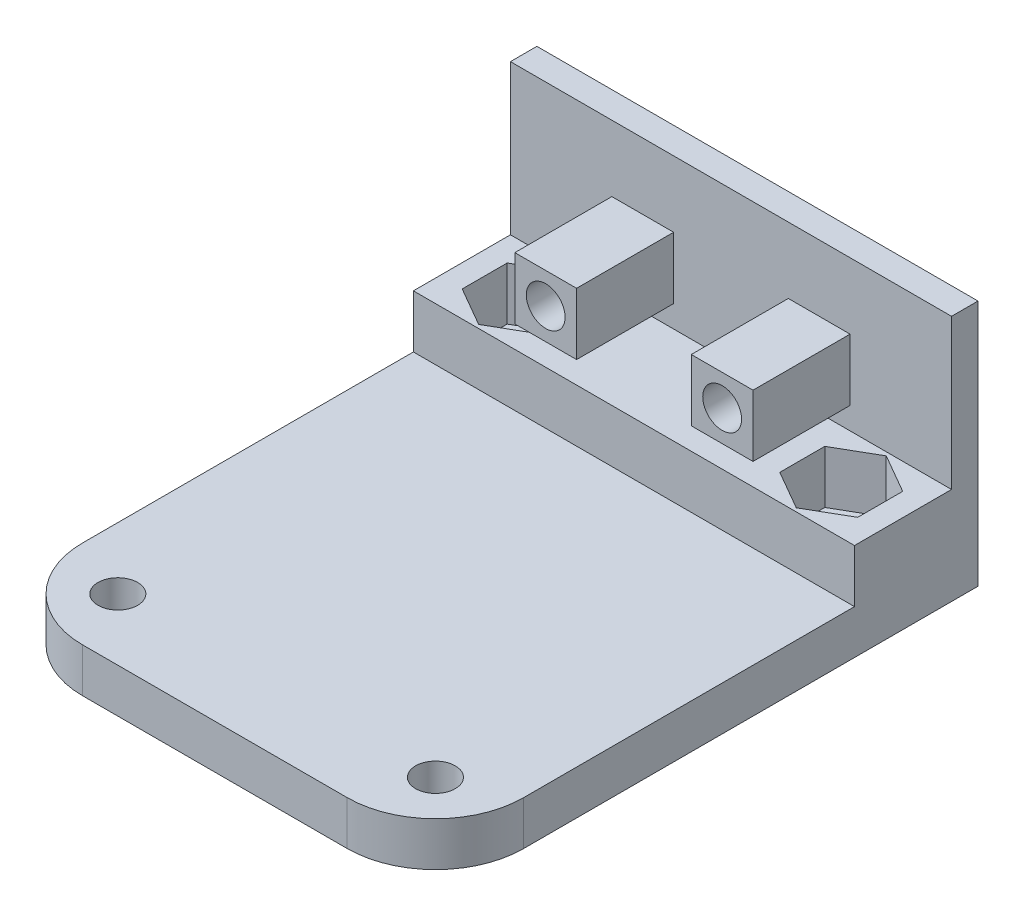
SolidWorks part; units mm, degrees
ref_plane "Front Plane" through (0, 0, 0) normal (0, 0, 1) x (1, 0, 0)
ref_plane "Top Plane" through (0, 0, 0) normal (0, 1, 0) x (1, 0, 0)
ref_plane "Right Plane" through (0, 0, 0) normal (1, 0, 0) x (0, 0, -1)
sketch "Sketch1" plane through (0, 0, 0) normal (0, 0, 1) x (1, 0, 0)
  line L1 (-25, 16.5) -> (25, 16.5)
  line L2 (-25, 16.5) -> (-25, -16.5)
  line L3 (-25, -16.5) -> (25, -16.5)
  line L4 (25, 16.5) -> (25, -16.5)
  line L5 (-25, 16.5) -> (25, -16.5) construction
  line L6 (-25, -16.5) -> (25, 16.5) construction
  point P0 (0, 0)
  dimension "D1" = 33
  dimension "D2" = 50
extrude "Boss-Extrude1" add sketch "Sketch1" along normal blind 3 contours L2 L3 L4 L1
sketch "Sketch2" plane through (0, 0, 3) normal (0, 0, 1) x (1, 0, 0)
  line L0 (25, 16.5) -> (25, -16.5) construction
  line L1 (-25, -16.5) -> (25, -16.5)
  line L2 (-25, -16.5) -> (-25, -11.5)
  line L3 (-25, -11.5) -> (25, -11.5)
  line L4 (25, -16.5) -> (25, -11.5)
  dimension "D1" = 5
extrude "Boss-Extrude2" add sketch "Sketch2" along normal blind 58.5
sketch "Sketch3" plane through (0, -11.5, 0) normal (0, 1, 0) x (1, 0, 0)
  line L0 (-25, -51.5) -> (-25, -61.5)
  line L1 (-25, -61.5) -> (-15, -61.5)
  line L2 (15, -61.5) -> (25, -61.5)
  line L3 (25, -61.5) -> (25, -51.5)
  arc A1 (15, -61.5) -> (25, -51.5) centre (15, -51.5) ccw construction
  arc A2 (15, -61.5) -> (25, -51.5) centre (15, -51.5) ccw
  arc A3 (-25, -51.5) -> (-15, -61.5) centre (-15, -51.5) ccw construction
  arc A4 (-25, -51.5) -> (-15, -61.5) centre (-15, -51.5) ccw
  circle A5 centre (-18, -54.5) radius 2.2479 construction
  circle A6 centre (-18, -54.5) radius 2.2479
  circle A7 centre (18, -54.5) radius 2.2479 construction
  circle A8 centre (18, -54.5) radius 2.2479
  circle A9 centre (-18, -8.5) radius 2.2479 construction
  circle A10 centre (-18, -8.5) radius 2.2479
  circle A11 centre (18, -8.5) radius 2.2479 construction
  circle A12 centre (18, -8.5) radius 2.2479
extrude "Cut-Extrude1" cut sketch "Sketch3" against normal up to surface (5 mm away) up to face at (0, -16.5, 30.75)
sketch "Sketch4" plane through (0, 0, 3) normal (0, 0, 1) x (1, 0, 0)
  line L5 (-13.5006, 4) -> (-6.5006, 4)
  line L6 (-13.5006, 4) -> (-13.5006, -3)
  line L7 (-13.5006, -3) -> (-6.5006, -3)
  line L8 (-6.5006, 4) -> (-6.5006, -3)
  line L9 (-13.5006, 4) -> (-6.5006, -3) construction
  line L10 (-13.5006, -3) -> (-6.5006, 4) construction
  line L11 (6.4994, 4) -> (13.4994, 4)
  line L12 (6.4994, 4) -> (6.4994, -3)
  line L13 (6.4994, -3) -> (13.4994, -3)
  line L14 (13.4994, 4) -> (13.4994, -3)
  line L15 (6.4994, 4) -> (13.4994, -3) construction
  line L16 (6.4994, -3) -> (13.4994, 4) construction
  circle A0 centre (-10.0006, 0.5) radius 2.2 construction
  circle A1 centre (-10.0006, 0.5) radius 2.2
  circle A2 centre (9.9994, 0.5) radius 2.2 construction
  circle A3 centre (9.9994, 0.5) radius 2.2
  dimension "D1" = 7
extrude "Boss-Extrude3" add sketch "Sketch4" along normal blind 11
sketch "Sketch5" plane through (0, 0, 14) normal (0, 0, 1) x (1, 0, 0)
  circle A0 centre (9.9994, 0.5) radius 2.2 construction
  circle A1 centre (9.9994, 0.5) radius 2.2
  circle A2 centre (-10.0006, 0.5) radius 2.2 construction
  circle A3 centre (-10.0006, 0.5) radius 2.2
extrude "Cut-Extrude2" cut sketch "Sketch5" against normal up to surface (14 mm away) up to face at (0, 0, 0)
sketch "Sketch6" plane through (0, 0, 3) normal (0, 0, 1) x (1, 0, 0)
  line L0 (25, 16.5) -> (25, -11.5) construction
  line L1 (-25, 16.5) -> (25, 16.5)
  line L2 (-25, 16.5) -> (-25, 11.5)
  line L3 (-25, 11.5) -> (25, 11.5)
  line L4 (25, 16.5) -> (25, 11.5)
  dimension "D1" = 5
extrude "Cut-Extrude3" cut sketch "Sketch6" against normal up to surface (3 mm away) up to face at (7.7994, 0.5, 0)
sketch "Sketch7" plane through (0, -11.5, 0) normal (0, 1, 0) x (1, 0, 0)
  line L0 (25, -51.5) -> (25, -3) construction
  line L1 (-25, -3) -> (25, -3)
  line L2 (-25, -3) -> (-25, -14)
  line L3 (-25, -14) -> (25, -14)
  line L4 (25, -3) -> (25, -14)
  dimension "D1" = 11
extrude "Boss-Extrude4" add sketch "Sketch7" along normal blind 6
sketch "Sketch8" plane through (0, -5.5, 0) normal (0, 1, 0) x (1, 0, 0)
  line L1 (-18, -3.4) -> (-22.4167, -5.95)
  line L2 (-22.4167, -5.95) -> (-22.4167, -11.05)
  line L3 (-22.4167, -11.05) -> (-18, -13.6)
  line L4 (-18, -13.6) -> (-13.5833, -11.05)
  line L5 (-13.5833, -11.05) -> (-13.5833, -5.95)
  line L6 (-13.5833, -5.95) -> (-18, -3.4)
  line L8 (0, -18.15) -> (0, 18.15) construction
  line L9 (13.5833, -5.95) -> (18, -3.4)
  line L10 (13.5833, -11.05) -> (13.5833, -5.95)
  line L11 (18, -13.6) -> (13.5833, -11.05)
  line L12 (22.4167, -11.05) -> (18, -13.6)
  line L13 (22.4167, -5.95) -> (22.4167, -11.05)
  line L14 (18, -3.4) -> (22.4167, -5.95)
  circle A1 centre (-18, -8.5) radius 2.2479 construction
  circle A2 centre (-18, -8.5) radius 4.4167 construction
  circle A3 centre (18, -8.5) radius 4.4167 construction
  circle A4 centre (18, -8.5) radius 2.2479 construction
  dimension "D1" = 5.1
extrude "Cut-Extrude4" cut sketch "Sketch8" against normal blind 6
